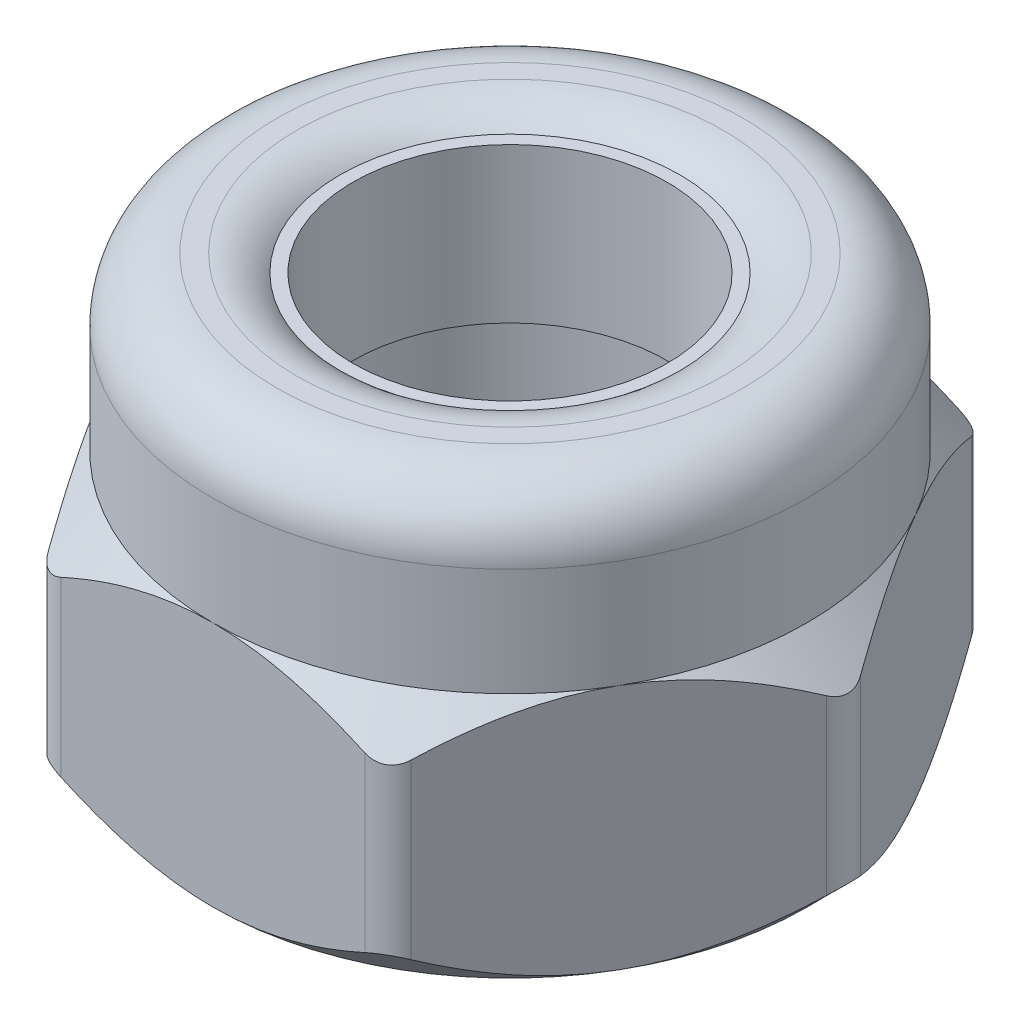
SolidWorks part; units mm, degrees
material "铸造碳钢"
ref_plane "Front" through (0, 0, 0) normal (0, 0, 1) x (1, 0, 0)
ref_plane "Top" through (0, 0, 0) normal (0, 1, 0) x (1, 0, 0)
ref_plane "Right" through (0, 0, 0) normal (1, 0, 0) x (0, 0, -1)
sketch "草图1" plane through (0, 0, 0) normal (0, 1, 0) x (1, 0, 0)
  line L1 (4.0415, 0) -> (2.0207, 3.5)
  line L2 (2.0207, 3.5) -> (-2.0207, 3.5)
  line L3 (-2.0207, 3.5) -> (-4.0415, 0)
  line L4 (-4.0415, 0) -> (-2.0207, -3.5)
  line L5 (-2.0207, -3.5) -> (2.0207, -3.5)
  line L6 (2.0207, -3.5) -> (4.0415, 0)
  circle A0 centre (0, 0) radius 3.5 construction
  dimension "六角对边长" = 7
extrude "凸台-拉伸1" add sketch "草图1" along normal mid plane 2.9
sketch "草图3" plane through (0, 1.45, 0) normal (0, 1, 0) x (1, 0, 0)
  circle A0 centre (0, 0) radius 3.5
  dimension "圆形外直径" = 7
extrude "凸台-拉伸2" add sketch "草图3" along normal blind 2.02
sketch "草图4" plane through (0, 3.47, 0) normal (0, 1, 0) x (1, 0, 0)
  circle A0 centre (0, 0) radius 2
  dimension "螺母内径" = 4
extrude "切除-拉伸1" cut sketch "草图4" against normal through all
sketch "草图5" plane through (0, 3.47, 0) normal (0, 1, 0) x (1, 0, 0)
  circle A0 centre (0, 0) radius 2
  circle A1 centre (0, 0) radius 1.85
  dimension "橡胶内径" = 3.7
  dimension "橡皮圈外直径" = 4
extrude "凸台-拉伸3" add sketch "草图5" against normal up to surface (2.02 mm away) from offset 0.2 up to face at (-3.5242, 1.45, 0) offset against normal yes
fillet "圆角1" radius 0.75 2 edges at (0, 3.47, 2) (0, 3.47, 3.5)
sketch "草图6" plane through (0, 0, 0) normal (0, 0, 1) x (1, 0, 0)
  line L0 (0, -1000) -> (0, 49000) construction
  line L1 (-1000, 0) -> (49000, 0) construction
  line L2 (-4.0415, 1.45) -> (-4.0415, 0.9085)
  line L3 (-4.0415, 0.9085) -> (-3.5, 1.45)
  line L4 (-3.5, 1.45) -> (-4.0415, 1.45)
  line L5 (0, 1.45) -> (-3.0311, 1.45) construction
  line L6 (-4.0415, 1.45) -> (-4.0415, -1.45) construction
  line L7 (-3.5, -998.4247) -> (-3.5, 49001.5753) construction
  line L8 (-3.5, 2.72) -> (-3.5, 1.45) construction
  line L9 (-4.0415, -1.45) -> (-4.0415, -0.9085)
  line L10 (-4.0415, -0.9085) -> (-3.5, -1.45)
  line L11 (-3.5, -1.45) -> (-4.0415, -1.45)
  dimension "D1" = 45
revolve "切除-旋转1" cut sketch "草图6" angle 360 about L0
fillet "圆角3" radius 0.4 6 edges at (-4.0415, 0, 0) (-2.0207, 0, -3.5) (2.0207, 0, -3.5) (4.0415, 0, 0) (2.0207, 0, 3.5) (-2.0207, 0, 3.5)
other "冻结***"
